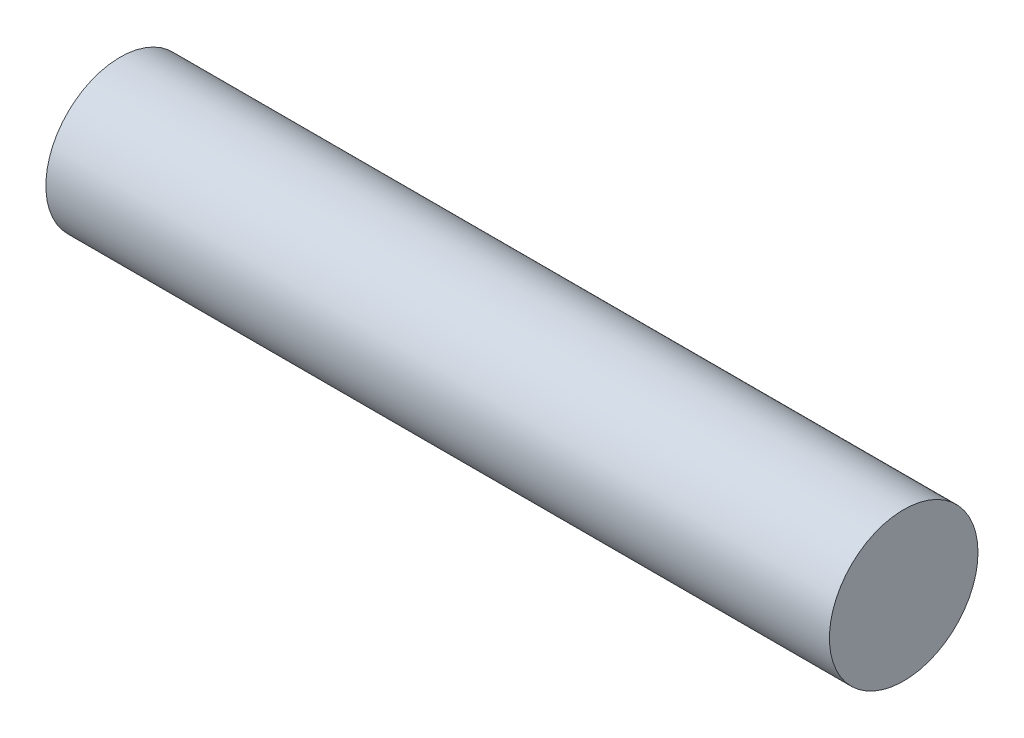
SolidWorks part; units mm, degrees
ref_plane "Front Plane" through (0, 0, 0) normal (0, 0, 1) x (1, 0, 0)
ref_plane "Top Plane" through (0, 0, 0) normal (0, 1, 0) x (1, 0, 0)
ref_plane "Right Plane" through (0, 0, 0) normal (1, 0, 0) x (0, 0, -1)
sketch "Sketch1" plane through (0, 0, 0) normal (1, 0, 0) x (0, 0, -1)
  circle A0 centre (0, 0) radius 1.505
  dimension "D1" = 3.0099
extrude "Boss-Extrude1" add sketch "Sketch1" along normal mid plane 15.875
